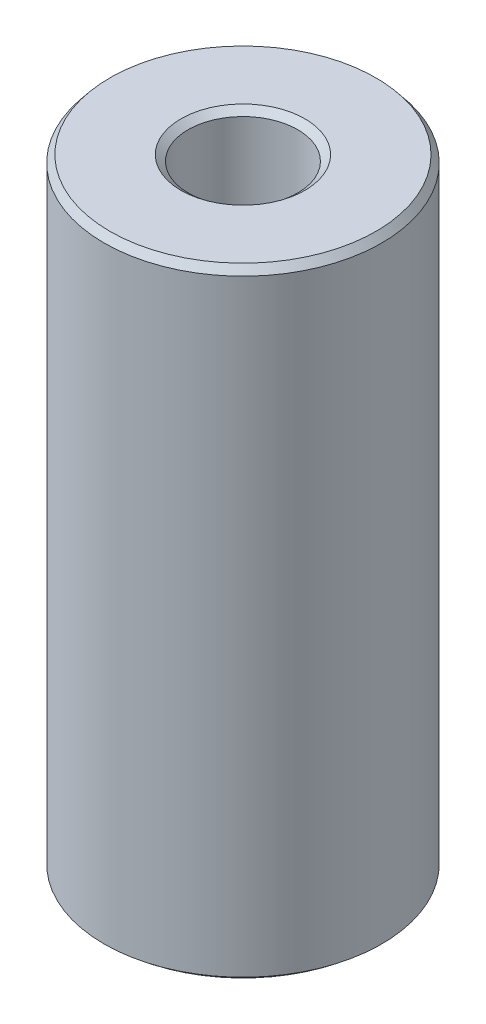
SolidWorks part; units mm, degrees
ref_plane "Front Plane" through (0, 0, 0) normal (0, 0, 1) x (1, 0, 0)
ref_plane "Top Plane" through (0, 0, 0) normal (0, 1, 0) x (1, 0, 0)
ref_plane "Right Plane" through (0, 0, 0) normal (1, 0, 0) x (0, 0, -1)
sketch "Sketch1" plane through (0, 0, 0) normal (0, 1, 0) x (1, 0, 0)
  circle A0 centre (0, 0) radius 57.5
  dimension "SLEEVE_OD" = 115
extrude "Boss-Extrude1" add sketch "Sketch1" along normal blind 256.8771
sketch "Sketch2" plane through (0, 0, 0) normal (0, 1, 0) x (1, 0, 0)
  circle A0 centre (0, 0) radius 22.7078
  dimension "BORE_D" = 45.4156
extrude "Cut-Extrude1" cut sketch "Sketch2" along normal through all
chamfer "Chamfer1" distance 2.9812 angle 38.844 4 edges at (0, 256.8771, 22.7078) (0, 0, 22.7078) (0, 0, 57.5) (0, 256.8771, 57.5) first distance on face at (0, 256.8771, 22.7078) first distance on face at (0, 0, 22.7078) first distance on face at (0, 256.8771, 57.5)
